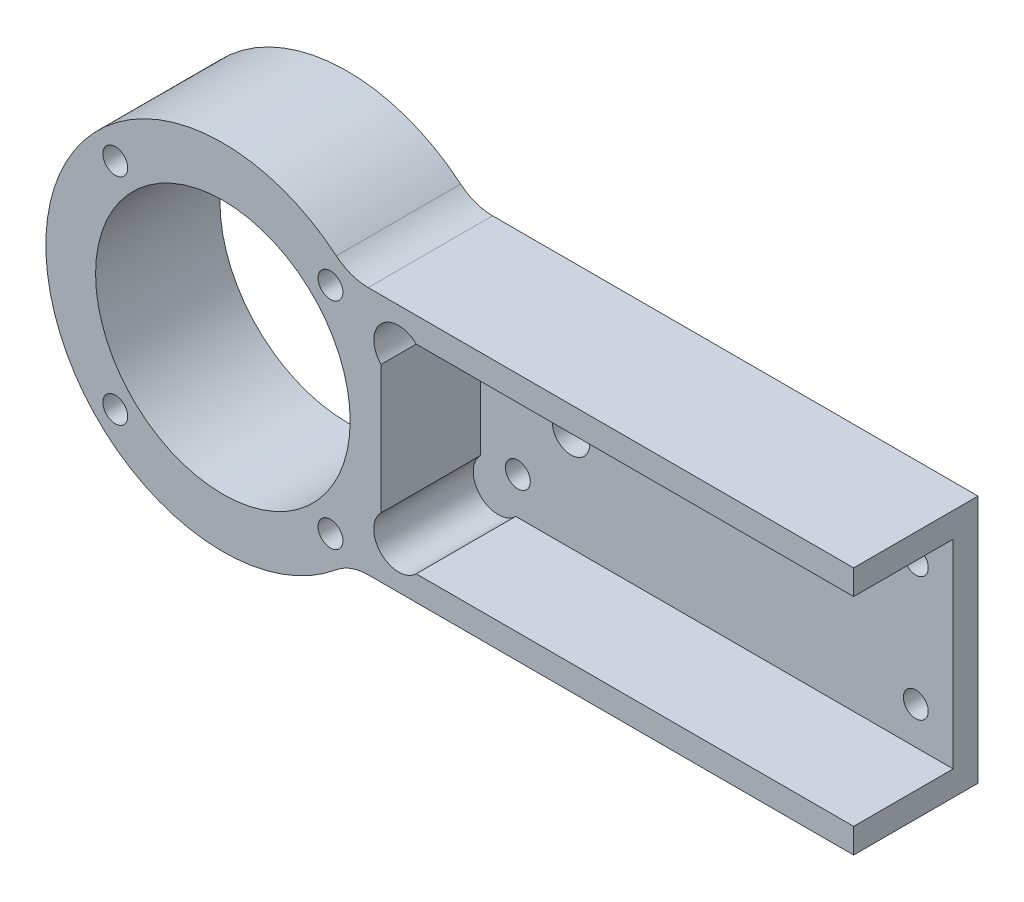
SolidWorks part; units mm, degrees
material "1060 Alloy"
ref_plane "Front Plane" through (0, 0, 0) normal (0, 0, 1) x (1, 0, 0)
ref_plane "Top Plane" through (0, 0, 0) normal (0, 1, 0) x (1, 0, 0)
ref_plane "Right Plane" through (0, 0, 0) normal (1, 0, 0) x (0, 0, -1)
sketch "Sketch1" plane through (0, 0, 0) normal (0, 0, 1) x (1, 0, 0)
  line L0 (32.1711, 31.75) -> (161.036, 31.75)
  line L1 (32.1711, -31.75) -> (161.036, -31.75)
  line L3 (161.036, 31.75) -> (161.036, 25.4)
  line L4 (161.036, -31.75) -> (161.036, -25.4)
  line L5 (161.036, 31.75) -> (161.036, -31.75) construction
  line L6 (161.036, 25.4) -> (40.386, 25.4)
  line L7 (40.386, 25.4) -> (40.386, -25.4)
  line L8 (40.386, -25.4) -> (161.036, -25.4)
  line L9 (161.036, 25.4) -> (161.036, -25.4)
  circle A0 centre (0, 0) radius 32.5
  arc A1 (32.1711, 31.75) -> (32.1711, -31.75) centre (0, 0) ccw
  point P3 (161.036, 0)
  dimension "D1" = 65
  dimension "D4" = 12.7
  dimension "D6" = 40.386
  dimension "D2" = 63.5
  dimension "D3" = 120.65
  dimension "D5" = 6.35
extrude "Boss-Extrude2" add sketch "Sketch1" along normal blind 6.35 contours L0 A1 L1 L4 L8 L7 L6 L3 A0 | L9 L6 L7 L8 region at (33.1354, 0, 0) region at (100.711, 0, 0)
extrude "Boss-Extrude3" add sketch "Sketch1<3>" along normal blind 25.4 from surface contours L0 A1 L1 L4 L8 L7 L6 L3 A0 region at (33.1354, 0, 0) starting at face at (77.2608, 0, 6.35)
sketch "Sketch1<3>" plane through (0, 0, 0) normal (0, 0, 1) x (1, 0, 0) same geometry as "Sketch1"
sketch "Sketch2" plane through (0, 0, 6.35) normal (0, 0, 1) x (1, 0, 0)
  line L0 (161.036, -25.4) -> (161.036, 25.4) construction
  line L1 (40.386, -25.4) -> (40.386, 25.4) construction
  line L2 (-27.4711, 27.4711) -> (0, 0) construction
  line L3 (0, 0) -> (-27.4711, -27.4711) construction
  line L4 (40.386, 25.4) -> (161.036, 25.4) construction
  line L5 (40.386, 25.4) -> (161.036, 25.4) construction
  line L6 (161.036, -25.4) -> (40.386, -25.4) construction
  line L7 (161.036, -25.4) -> (40.386, -25.4) construction
  line L8 (0, 0) -> (27.4711, 27.4711) construction
  line L11 (0, 0) -> (27.4711, -27.4711) construction
  line L13 (0, 0) -> (-32.5, 0) construction
  circle A0 centre (49.911, 15.875) radius 3.175
  circle A1 centre (151.511, 15.875) radius 3.175
  circle A2 centre (151.511, -15.875) radius 3.175
  circle A3 centre (49.911, -15.875) radius 3.175
  circle A4 centre (27.4711, 27.4711) radius 3.175
  circle A5 centre (27.4711, -27.4711) radius 3.175
  circle A6 centre (-27.4711, -27.4711) radius 3.175
  circle A7 centre (-27.4711, 27.4711) radius 3.175
  circle A8 centre (0, 0) radius 32.5 construction
  circle A15 centre (0, 0) radius 38.85 construction
  arc A16 (32.1711, 31.75) -> (32.1711, -31.75) centre (0, 0) ccw construction
  dimension "D1" = 6.35
  dimension "D2" = 6.35
  dimension "D4" = 9.525
  dimension "D5" = 9.525
  dimension "D6" = 9.525
  dimension "D3" = 9.525
  dimension "D7" = 9.525
  dimension "D8" = 9.525
  dimension "D11" = 45
  dimension "D12" = 45
extrude "Cut-Extrude1" cut sketch "Sketch2" against normal through all and the other way through all
sketch "Sketch3" plane through (0, 0, 31.75) normal (0, 0, 1) x (1, 0, 0)
  line L0 (40.386, 25.4) -> (49.3663, 16.4197) construction
  line L1 (40.386, 25.4) -> (161.036, 25.4) construction
  line L2 (40.386, 0) -> (32.5, 0) construction
  line L3 (40.386, -25.4) -> (40.386, 25.4) construction
  circle A0 centre (44.8761, 20.9099) radius 6.35
  circle A1 centre (0, 0) radius 32.5 construction
  circle A2 centre (44.8761, -20.9099) radius 6.35
  dimension "D1" = 12.7
  dimension "D2" = 45
extrude "Cut-Extrude2" cut sketch "Sketch3" against normal up to surface (25.4 mm away) up to face at (53.086, 15.875, 6.35)
sketch "Sketch4" plane through (0, 0, 0) normal (0, 0, -1) x (-1, 0, 0)
  line L0 (-31.75, 54.9926) -> (0, 0) construction
  line L1 (0, 0) -> (31.75, 54.9926) construction
  line L2 (-32.1711, -31.75) -> (-161.036, -31.75) construction
  line L3 (0, 0) -> (63.5, 0) construction
  line L4 (0, 0) -> (31.75, -54.9926) construction
  line L9 (-51.2937, 31.75) -> (-32.1711, 31.75)
  line L10 (-32.1711, 31.75) -> (-161.036, 31.75) construction
  line L11 (-32.1711, -31.75) -> (-51.2937, -31.75)
  line L12 (0, 0) -> (-63.5, 0) construction
  line L13 (0, 0) -> (-31.75, -54.9926) construction
  arc A1 (-40.8506, -48.6156) -> (-40.8506, 48.6156) centre (0, 0) ccw construction
  arc A2 (-20.7603, 56.6402) -> (-38.6717, 46.2991) centre (-31.75, 54.9926) ccw
  arc A8 (38.6717, 46.2991) -> (20.7603, 56.6402) centre (31.75, 54.9926) ccw
  arc A9 (59.432, -10.3411) -> (59.432, 10.3411) centre (63.5, 0) ccw
  arc A10 (20.7603, -56.6402) -> (38.6717, -46.2991) centre (31.75, -54.9926) ccw
  arc A11 (-38.6717, -46.2991) -> (-20.7603, -56.6402) centre (-31.75, -54.9926) ccw
  circle A13 centre (-31.75, 54.9926) radius 4.7625
  arc A14 (-38.6717, 46.2991) -> (-51.2937, 31.75) centre (0, 0) ccw
  circle A15 centre (31.75, 54.9926) radius 4.7625
  arc A16 (-32.1711, -31.75) -> (-32.1711, 31.75) centre (0, 0) ccw construction
  arc A17 (20.7603, 56.6402) -> (-20.7603, 56.6402) centre (0, 0) ccw
  circle A18 centre (63.5, 0) radius 4.7625
  circle A19 centre (31.75, -54.9926) radius 4.7625
  arc A20 (59.432, 10.3411) -> (38.6717, 46.2991) centre (0, 0) ccw
  arc A21 (38.6717, -46.2991) -> (59.432, -10.3411) centre (0, 0) ccw
  circle A22 centre (-31.75, -54.9926) radius 4.7625
  arc A23 (-20.7603, -56.6402) -> (20.7603, -56.6402) centre (0, 0) ccw
  arc A24 (-32.1711, -31.75) -> (-32.1711, 31.75) centre (0, 0) ccw
  arc A25 (-51.2937, -31.75) -> (-38.6717, -46.2991) centre (0, 0) ccw
  circle A26 centre (-63.5, 0) radius 4.7625
  point P48 (0, 0)
  dimension "D1" = 6.35
  dimension "D2" = 127
  dimension "D3" = 6
  dimension "D8" = 60.325
  dimension "D9" = 9.525
extrude "Boss-Extrude5" [suppressed] add sketch "Sketch4" against normal blind 6.35
extrude "Cut-Extrude3" cut sketch "Sketch4<3>" against normal blind 6.35 contours A26 region at (63.5, 0, 0)
sketch "Sketch4<3>" plane through (0, 0, 0) normal (0, 0, -1) x (-1, 0, 0) same geometry as "Sketch4"
fillet "Fillet1" radius 12.7 2 edges at (32.1711, -31.75, 15.875) (32.1711, 31.75, 15.875)
fillet "Fillet2" [suppressed] radius 12.7
